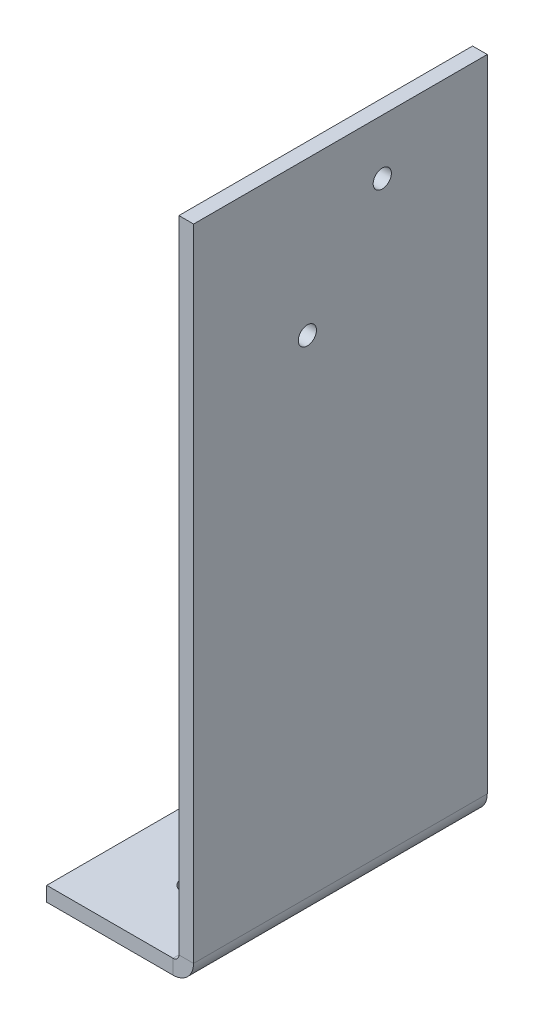
SolidWorks part; units mm, degrees
note: The reader was unsure of these and kept them because the rebuilt part matched: flange length of "Edge-Flange1".
ref_plane "Front Plane" through (0, 0, 0) normal (0, 0, 1) x (1, 0, 0)
ref_plane "Top Plane" through (0, 0, 0) normal (0, 1, 0) x (1, 0, 0)
ref_plane "Right Plane" through (0, 0, 0) normal (1, 0, 0) x (0, 0, -1)
sketch "Sketch2" plane through (0, 0, 0) normal (0, 1, 0) x (1, 0, 0)
  line L1 (0, 0) -> (25.4, 0)
  line L2 (0, 0) -> (0, 50.8)
  line L3 (0, 50.8) -> (25.4, 50.8)
  line L4 (25.4, 0) -> (25.4, 50.8)
  dimension "D1" = 50.8
  dimension "D2" = 25.4
base flange "Base-Flange1" sketch "Sketch2" thickness 2.54 reverse thickness direction no parameters "D1"=1
edge flange "Edge-Flange1" sketch "Sketch9" flange angle 90 flange length 114.3 flange position material inside bend radius 1 thickness 2.54 parameters "D6"=10
sketch "Sketch9" plane through (25.4, 0, 0) normal (1, 0, 0) x (0, 0, -1)
  line L2 (0, 0) -> (0, 111.76)
  line L3 (0, 111.76) -> (50.8, 111.76)
  line L4 (50.8, 111.76) -> (50.8, 0)
  line L5 (0, 0) -> (50.8, 0) construction
  line L6 (0, 0) -> (50.8, 0)
bend "EdgeBend1" bend radius 1 bend angle 90 parameters "D5"=1
sketch "Sketch10" plane through (0, -2.54, 0) normal (0, -1, 0) x (1, 0, 0)
  line L0 (12.7, -50.8) -> (12.7, -38.1)
  line L2 (21.86, -50.8) -> (0, -50.8) construction
  line L3 (12.7, -38.1) -> (12.7, -12.7)
  circle A0 centre (12.7, -38.1) radius 2.032
  circle A2 centre (12.7, -12.7) radius 2.032
  dimension "D3" = 4.064
  dimension "D4" = 4.064
  dimension "D1" = 12.7
  dimension "D2" = 25.4
extrude "Cut-Extrude1" cut sketch "Sketch10" against normal through all
sketch "Sketch11" plane through (22.86, 0, 0) normal (-1, 0, 0) x (0, 0, 1)
  line L0 (-50.8, 111.76) -> (-50.8, 102.2604)
  line L1 (-50.8, 1) -> (-50.8, 111.76) construction
  line L2 (-50.8, 102.2604) -> (-32.639, 102.2604)
  line L3 (-32.639, 102.2604) -> (-19.685, 102.2604)
  line L4 (-19.685, 102.2604) -> (-19.685, 85.2424)
  circle A0 centre (-32.639, 102.2604) radius 1.5748
  circle A1 centre (-19.685, 85.2424) radius 1.5748
  dimension "D5" = 3.1496
  dimension "D6" = 3.1496
  dimension "D1" = 9.4996
  dimension "D2" = 18.161
  dimension "D3" = 12.954
  dimension "D4" = 17.018
extrude "Cut-Extrude2" cut sketch "Sketch11" against normal through all
sketch "Bend-Lines1" [suppressed] plane through (0, 0, 0) normal (0, 1, 0) x (1, 0, 0)
sketch "Bounding-Box1" [suppressed] plane through (0, 0, 0) normal (0, 1, 0) x (1, 0, 0)
sheet metal parameters "Sheet-Metal1" thickness 2.54 parameters "D1"=1
flat pattern "Flat-Pattern1" [suppressed]
sketch "Bend-Lines2" plane through (0, 0, 0) normal (0, 1, 0) x (1, 0, 0)
sketch3d "Bounding-Box2" [suppressed]
  line L0 (-50.8, 25.4, 0) -> (0, 25.4, 0) construction
  line L1 (-50.8, 0, 0) -> (0, 0, 0) construction
  line L2 (-50.8, 25.4, 0) -> (-50.8, 0, 0) construction
  line L3 (0, 25.4, 0) -> (0, 0, 0) construction
sheet metal parameters "Sheet-Metal2" thickness 2.54 parameters "D1"=1
flat pattern "Flat-Pattern1"
sketch "Bend-Lines2" plane through (0, 0, 0) normal (0, 1, 0) x (1, 0, 0)
  line L0 (49.0429, 0) -> (49.0429, 25.4) construction
  line L1 (49.0429, 0) -> (49.0429, 25.4) construction
sketch3d "Bounding-Box2" [suppressed]
  line L0 (161.5857, 25.4, 0) -> (0, 25.4, 0) construction
  line L1 (161.5857, 0, 0) -> (0, 0, 0) construction
  line L2 (161.5857, 25.4, 0) -> (161.5857, 0, 0) construction
  line L3 (0, 25.4, 0) -> (0, 0, 0) construction
bend of the flat pattern "Flatten-<EdgeBend1>1"
sheet metal parameters "Sheet-Metal3" thickness 2.54 parameters "D1"=1
flat pattern "Flat-Pattern1"
sketch "Bend-Lines2" plane through (0, 0, 0) normal (0, 1, 0) x (1, 0, 0)
  line L0 (49.0429, 0) -> (49.0429, 25.4) construction
  line L1 (49.0429, 0) -> (49.0429, 25.4) construction
sketch3d "Bounding-Box2" [suppressed]
  line L0 (161.5857, 25.4, 0) -> (0, 25.4, 0) construction
  line L1 (161.5857, 0, 0) -> (0, 0, 0) construction
  line L2 (161.5857, 25.4, 0) -> (161.5857, 0, 0) construction
  line L3 (0, 25.4, 0) -> (0, 0, 0) construction
bend of the flat pattern "Flatten-<EdgeBend1>1"
sheet metal parameters "Sheet-Metal4" thickness 2.54 parameters "D1"=1
flat pattern "Flat-Pattern1"
sketch "Bend-Lines2" plane through (0, 0, 0) normal (0, 1, 0) x (1, 0, 0)
  line L0 (23.6429, 0) -> (23.6429, 50.8) construction
  line L1 (23.6429, 0) -> (23.6429, 50.8) construction
sketch3d "Bounding-Box2" [suppressed]
  line L0 (136.1857, 50.8, 0) -> (0, 50.8, 0) construction
  line L1 (136.1857, 0, 0) -> (0, 0, 0) construction
  line L2 (136.1857, 50.8, 0) -> (136.1857, 0, 0) construction
  line L3 (0, 50.8, 0) -> (0, 0, 0) construction
bend of the flat pattern "Flatten-<EdgeBend1>1"
